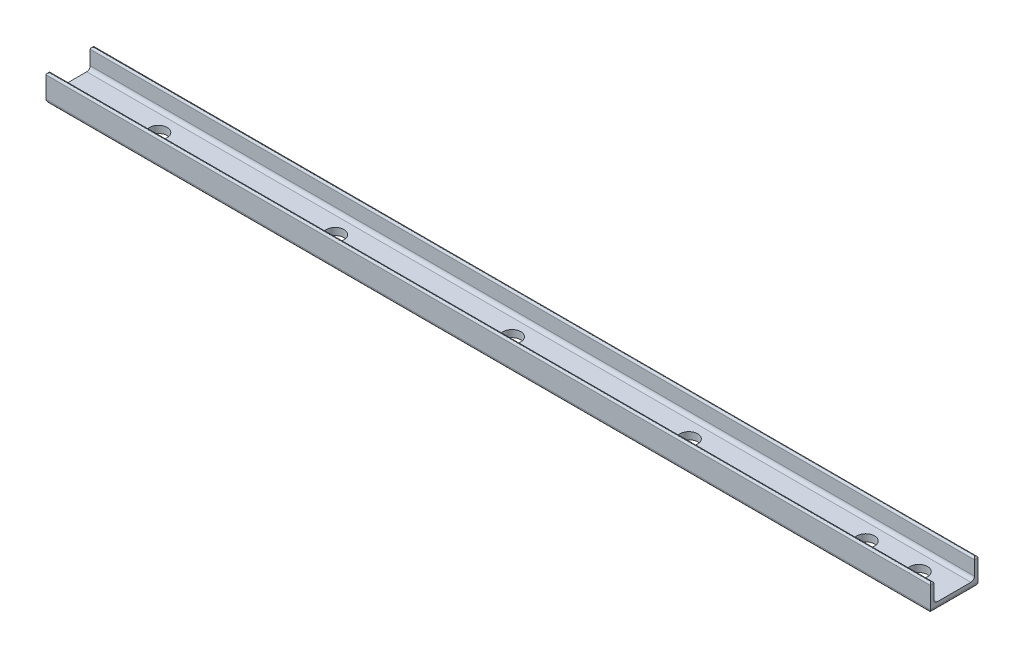
SolidWorks part; units mm, degrees
ref_plane "Front Plane" through (0, 0, 0) normal (0, 0, 1) x (1, 0, 0)
ref_plane "Top Plane" through (0, 0, 0) normal (0, 1, 0) x (1, 0, 0)
ref_plane "Right Plane" through (0, 0, 0) normal (1, 0, 0) x (0, 0, -1)
sketch "Sketch1" plane through (0, 0, 0) normal (0, 1, 0) x (1, 0, 0)
  line L0 (-125, 0) -> (125, 0) construction
  line L1 (-125, 6.75) -> (125, 6.75)
  line L2 (-125, 6.75) -> (-125, -6.75)
  line L3 (-125, -6.75) -> (125, -6.75)
  line L4 (125, 6.75) -> (125, -6.75)
  line L5 (-125, 6.75) -> (125, -6.75) construction
  line L6 (-125, -6.75) -> (125, 6.75) construction
  circle A0 centre (0, 0) radius 2.5
  circle A1 centre (-50, 0) radius 2.5
  circle A2 centre (-100, 0) radius 2.5
  circle A3 centre (50, 0) radius 2.5
  circle A4 centre (100, 0) radius 2.5
  circle A5 centre (115, 0) radius 2.5
  point P0 (0, 0)
  dimension "D3" = 5
  dimension "D4" = 5
  dimension "D5" = 5
  dimension "D6" = 5
  dimension "D7" = 5
  dimension "D8" = 5
  dimension "D1" = 13.5
  dimension "D2" = 250
  dimension "D9" = 50
  dimension "D10" = 50
  dimension "D11" = 50
  dimension "D12" = 50
  dimension "D13" = 15
extrude "Boss-Extrude1" add sketch "Sketch1" along normal blind 2
sketch "Sketch3" plane through (0, 2, 0) normal (0, 1, 0) x (1, 0, 0)
  line L0 (125, -6.75) -> (125, 6.75) construction
  line L1 (-125, 6.75) -> (125, 6.75)
  line L2 (-125, 6.75) -> (-125, 5.75)
  line L3 (-125, 5.75) -> (125, 5.75)
  line L4 (125, 6.75) -> (125, 5.75)
  line L6 (-125, -6.75) -> (125, -6.75)
  line L7 (-125, -6.75) -> (-125, -5.75)
  line L8 (-125, -5.75) -> (125, -5.75)
  line L9 (125, -6.75) -> (125, -5.75)
  dimension "D1" = 1
  dimension "D2" = 1
extrude "Boss-Extrude2" add sketch "Sketch3" along normal blind 5.5
fillet "Fillet1" radius 1 6 edges at (125, 0, 0) (0, 2, 5.75) (0, 2, -5.75) (-125, 0, 0) (0, 0, -6.75) (0, 0, 6.75)
fillet "Fillet2" radius 0.5 8 edges at (0, 7.5, 5.75) (125, 7.5, 6.25) (0, 7.5, 6.75) (-125, 7.5, 6.25) (0, 7.5, -6.75) (125, 7.5, -6.25) (0, 7.5, -5.75) (-125, 7.5, -6.25)
equation "\"D4@Sketch1\"=\"D3@Sketch1\""
equation "\"D5@Sketch1\"=\"D3@Sketch1\""
equation "\"D6@Sketch1\"=\"D3@Sketch1\""
equation "\"D7@Sketch1\"=\"D3@Sketch1\""
equation "\"D8@Sketch1\"=\"D3@Sketch1\""
